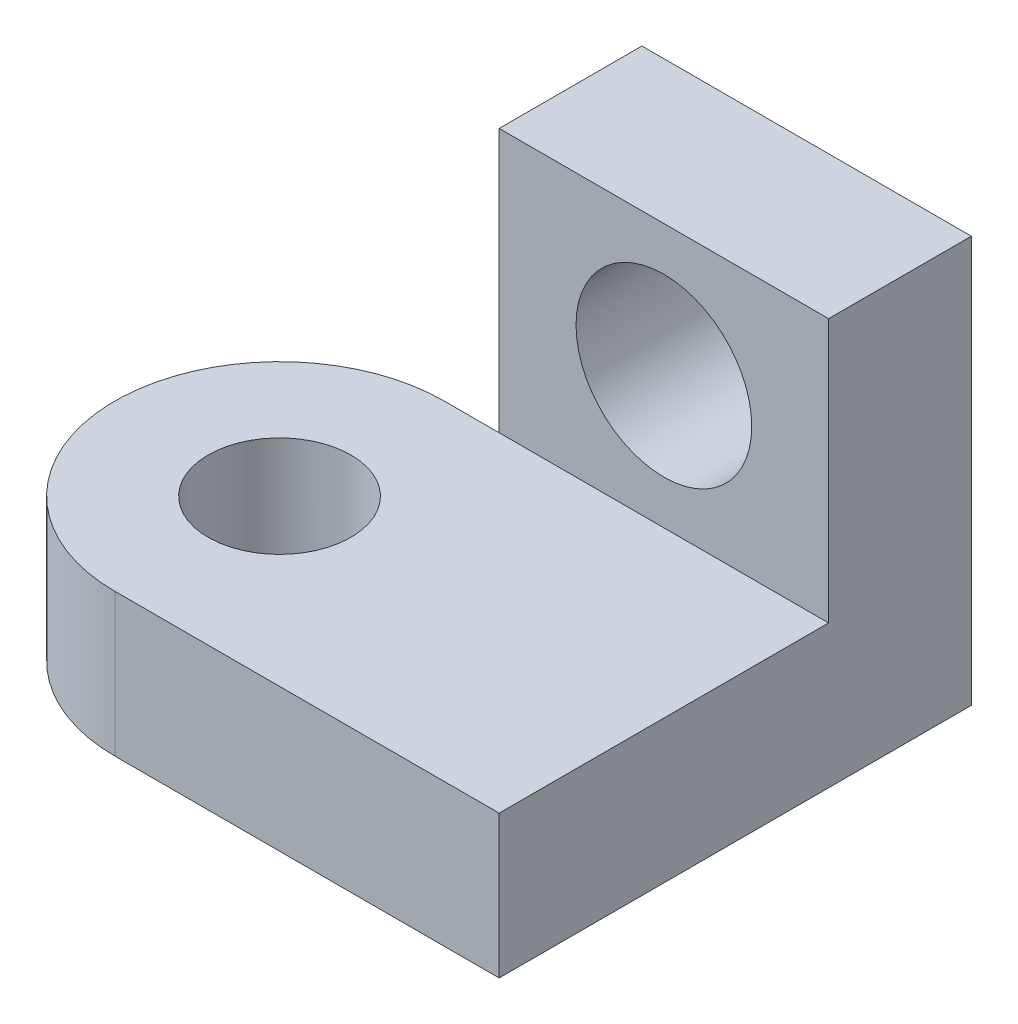
SolidWorks part; units mm, degrees
ref_plane "Front Plane" through (0, 0, 0) normal (0, 0, 1) x (1, 0, 0)
ref_plane "Top Plane" through (0, 0, 0) normal (0, 1, 0) x (1, 0, 0)
ref_plane "Right Plane" through (0, 0, 0) normal (1, 0, 0) x (0, 0, -1)
sketch "Sketch1" plane through (0, 0, 0) normal (0, 0, 1) x (1, 0, 0)
  line L1 (-30, 13) -> (0, 13)
  line L2 (-30, 13) -> (-30, 37)
  line L3 (-30, 37) -> (0, 37)
  line L4 (0, 13) -> (0, 37)
  line L5 (0, 13) -> (-50, 13)
  line L6 (0, 13) -> (0, 0)
  line L7 (0, 0) -> (-50, 0)
  line L8 (-50, 13) -> (-50, 0)
  circle A0 centre (-15, 25) radius 8
  point P7 (0, 0)
  point P13 (-14.481, 56.7391)
  dimension "D5" = 16
  dimension "D1" = 30
  dimension "D2" = 50
  dimension "D3" = 37
  dimension "D4" = 13
  dimension "D6" = 15
  dimension "D7" = 12
extrude "Boss-Extrude1" add sketch "Sketch1" along normal blind 13 contours L1 L4 L3 L2 A0 region at (-29.6158, 25, 0)
extrude "Boss-Extrude2" add sketch "Sketch1<3>" along normal blind 43 contours L5 L8 L7 L6 L1 region at (-25, 6.5, 0)
sketch "Sketch1<3>" plane through (0, 0, 0) normal (0, 0, 1) x (1, 0, 0) same geometry as "Sketch1"
sketch "Sketch2" plane through (0, 13, 0) normal (0, 1, 0) x (1, 0, 0)
  line L1 (-50, 0) -> (-30, 0)
  line L2 (-50, 0) -> (-50, -13)
  line L3 (-50, -13) -> (-30, -13)
  line L4 (-30, 0) -> (-30, -13)
extrude "Cut-Extrude1" cut sketch "Sketch2" against normal blind 43
sketch "Sketch3" plane through (0, 13, 0) normal (0, 1, 0) x (1, 0, 0)
  line L0 (0, -43) -> (-50, -43) construction
  line L1 (0, -43) -> (0, -13) construction
  line L2 (-50, -13) -> (-30, -13) construction
  line L3 (-35, -13) -> (-50, -13)
  line L4 (-50, -13) -> (-50, -28)
  line L5 (-50, -28) -> (-50, -43)
  line L6 (-50, -43) -> (-35, -43)
  arc A1 (-50, -28) -> (-35, -43) centre (-35, -28) ccw
  arc A2 (-35, -13) -> (-50, -28) centre (-35, -28) ccw
  point P1 (0, 0)
  line M8 (-30, -13) -> (-50, -13)
  line M9 (-50, -13) -> (-50, -43)
  line M10 (-50, -43) -> (0, -43)
  dimension "D2" = 35
extrude "Cut-Extrude3" cut sketch "Sketch3" against normal blind 43 contours A2 M8 M9 | A1 M9 M10 region at (-46.6495, 13, 16.3505) region at (-46.6495, 13, 39.6495)
sketch "Sketch4" plane through (0, 13, 0) normal (0, 1, 0) x (1, 0, 0)
  circle A0 centre (-35, -28) radius 6.5
  arc A1 (-35, -13) -> (-35, -43) centre (-35, -28) ccw construction
  point P2 (0, 0)
  dimension "D1" = 13
extrude "Cut-Extrude4" cut sketch "Sketch4" against normal blind 43 contours A0
